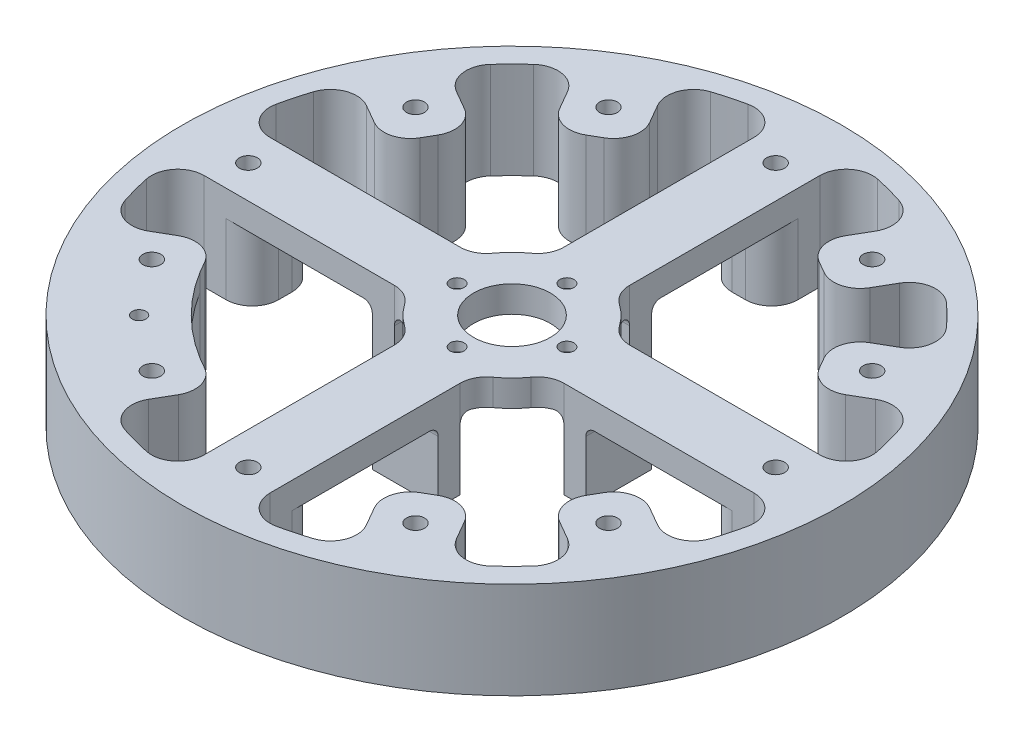
SolidWorks part; units mm, degrees
ref_plane "Front Plane" through (0, 0, 0) normal (0, 0, 1) x (1, 0, 0)
ref_plane "Top Plane" through (0, 0, 0) normal (0, 1, 0) x (1, 0, 0)
ref_plane "Right Plane" through (0, 0, 0) normal (1, 0, 0) x (0, 0, -1)
sketch "Sketch4" plane through (0, 0, 0) normal (0, 1, 0) x (1, 0, 0)
  circle A0 centre (0, 0) radius 75
  circle A1 centre (0, 0) radius 70
  dimension "D1" = 150
  dimension "D2" = 5
extrude "Boss-Extrude2" add sketch "Sketch4" along normal blind 22
sketch "Sketch5" plane through (0, 22, 0) normal (0, 1, 0) x (1, 0, 0)
  line L2 (-7.5, 69.5971) -> (-7.5, 51.5971)
  line L3 (-7.5, 51.5971) -> (7.5, 51.5971)
  line L4 (7.5, 69.5971) -> (7.5, 51.5971)
  circle A0 centre (0, 0) radius 70 construction
  arc A1 (-7.5, 69.5971) -> (7.5, 69.5971) centre (0, 0) cw
  circle A2 centre (0, 60) radius 2.05
  point P6 (0, 51.5971)
  dimension "D3" = 4.1
  dimension "D1" = 15
  dimension "D2" = 18
  dimension "D4" = 60
extrude "Boss-Extrude3" add sketch "Sketch5" against normal up to surface (22 mm away) up to face at (0, 0, 75)
fillet "Fillet1" radius 6 4 edges at (7.5, 11, -69.5971) (-7.5, 11, -69.5971) (7.5, 11, -51.5971) (-7.5, 11, -51.5971)
pattern_circular "CirPattern3" count 12 over 360 about axis through (0, 22, 0) along (0, 1, 0) of "Fillet1", "Boss-Extrude3"
sketch "Sketch1" plane through (0, 0, 0) normal (0, 1, 0) x (1, 0, 0)
  circle A0 centre (0, 0) radius 55
  circle A1 centre (0, 0) radius 75
  dimension "D1" = 150
  dimension "D2" = 110
extrude "Boss-Extrude1" [suppressed] add sketch "Sketch1" along normal blind 21.08
sketch "Sketch2" [suppressed] plane through (0, 21.08, 0) normal (0, 1, 0) x (1, 0, 0)
  circle A0 centre (0, 60) radius 2.05
  circle A1 centre (30, 51.9615) radius 2.05
  circle A2 centre (51.9615, 30) radius 2.05
  circle A3 centre (60, 0) radius 2.05
  circle A4 centre (51.9615, -30) radius 2.05
  circle A5 centre (30, -51.9615) radius 2.05
  circle A6 centre (0, -60) radius 2.05
  circle A7 centre (-30, -51.9615) radius 2.05
  circle A8 centre (-51.9615, -30) radius 2.05
  circle A9 centre (-60, 0) radius 2.05
  circle A10 centre (-51.9615, 30) radius 2.05
  circle A11 centre (-30, 51.9615) radius 2.05
  point P27 (0, 0)
  dimension "D1" = 4.1
  dimension "D2" = 60
  dimension "D3" = 12
extrude "Cut-Extrude1" [suppressed] cut sketch "Sketch2" against normal through all
sketch "Sketch3" [suppressed] plane through (0, 21.08, 0) normal (0, 1, 0) x (1, 0, 0)
  line L0 (0, 0) -> (0, 60) construction
  line L1 (0, 0) -> (30, 51.9615) construction
  line L2 (0, 0) -> (16.8232, 62.7852) construction
  circle A0 centre (16.8232, 62.7852) radius 7.5
  circle A1 centre (0, 0) radius 65 construction
  circle A2 centre (45.9619, 45.9619) radius 7.5
  circle A3 centre (62.7852, 16.8232) radius 7.5
  circle A4 centre (62.7852, -16.8232) radius 7.5
  circle A5 centre (45.9619, -45.9619) radius 7.5
  circle A6 centre (16.8232, -62.7852) radius 7.5
  circle A7 centre (-16.8232, -62.7852) radius 7.5
  circle A8 centre (-45.9619, -45.9619) radius 7.5
  circle A9 centre (-62.7852, -16.8232) radius 7.5
  circle A10 centre (-62.7852, 16.8232) radius 7.5
  circle A11 centre (-45.9619, 45.9619) radius 7.5
  circle A12 centre (-16.8232, 62.7852) radius 7.5
  point P30 (0, 0)
  dimension "D1" = 15
  dimension "D2" = 130
  dimension "D4" = 15
  dimension "D3" = 12
extrude "Cut-Extrude2" [suppressed] cut sketch "Sketch3" against normal through all
sketch "Sketch6" plane through (0, 22, 0) normal (0, 1, 0) x (1, 0, 0)
  line L0 (-7.5, 57.5971) -> (-7.5, 15.8667)
  line L1 (7.5, 57.5971) -> (7.5, 15.8667)
  line L2 (57.5971, 7.5) -> (15.8667, 7.5)
  line L3 (-57.5971, -7.5) -> (-15.8667, -7.5)
  line L5 (7.5, -15.8667) -> (7.5, -57.5971)
  line L6 (-7.5, -15.8667) -> (-7.5, -57.5971)
  line L7 (-15.8667, 7.5) -> (-57.5971, 7.5)
  line L8 (15.8667, -7.5) -> (57.5971, -7.5)
  line L9 (-57.5971, 7.5) -> (-57.5971, -7.5)
  line L10 (-7.5, -57.5971) -> (7.5, -57.5971)
  line L11 (57.5971, 7.5) -> (57.5971, -7.5)
  line L12 (-7.5, 57.5971) -> (7.5, 57.5971)
  arc A0 (-51.5971, 1.5) -> (-57.5971, 7.5) centre (-57.5971, 1.5) ccw construction
  arc A1 (7.5, -15.8667) -> (15.8667, -7.5) centre (0, 0) ccw
  arc A2 (15.8667, 7.5) -> (7.5, 15.8667) centre (0, 0) ccw
  arc A3 (-7.5, 15.8667) -> (-15.8667, 7.5) centre (0, 0) ccw
  arc A4 (-15.8667, -7.5) -> (-7.5, -15.8667) centre (0, 0) ccw
  circle A5 centre (-12.5, 0) radius 1.6
  circle A6 centre (0, 12.5) radius 1.6
  circle A7 centre (12.5, 0) radius 1.6
  circle A8 centre (0, -12.5) radius 1.6
  circle A9 centre (0, 0) radius 8.75
  point P40 (0, 0)
  dimension "D1" = 35.1
  dimension "D2" = 3.2
  dimension "D5" = 17.5
  dimension "D3" = 12.5
  dimension "D4" = 4
extrude "Boss-Extrude4" add sketch "Sketch6" against normal blind 6
sketch "Sketch7" plane through (0, 16, 0) normal (0, -1, 0) x (1, 0, 0)
  circle A0 centre (0, 12.5) radius 3.5
  circle A1 centre (12.5, 0) radius 3.5
  circle A2 centre (0, -12.5) radius 3.5
  circle A3 centre (-12.5, 0) radius 3.5
  point P12 (0, 0)
  dimension "D1" = 7
  dimension "D2" = 4
extrude "Cut-Extrude3" cut sketch "Sketch7" against normal blind 3.9
chamfer "Chamfer1" distance 1.9 angle 45 4 edges at (-12.5, 19.9, -3.5) (0, 19.9, -16) (12.5, 19.9, -3.5) (0, 19.9, 9)
fillet "Fillet2" radius 6 8 edges at (-7.5, 19, 15.8667) (-15.8667, 19, 7.5) (-15.8667, 19, -7.5) (-7.5, 19, -15.8667) (7.5, 19, -15.8667) (15.8667, 19, -7.5) (15.8667, 19, 7.5) (7.5, 19, 15.8667)
sketch "Sketch8" plane through (0, 16, 0) normal (0, -1, 0) x (1, 0, 0)
  line L0 (-19.2964, -7.5) -> (-57.5971, -7.5) construction
  line L1 (-19.2964, 7.5) -> (-24.2964, 7.5)
  line L2 (-19.2964, 7.5) -> (-19.2964, -7.5)
  line L3 (-19.2964, -7.5) -> (-24.2964, -7.5)
  line L4 (-24.2964, 7.5) -> (-24.2964, -7.5)
  line L5 (7.5, 57.5971) -> (7.5, 19.2964) construction
  line L6 (-7.5, 19.2964) -> (7.5, 19.2964)
  line L7 (-7.5, 19.2964) -> (-7.5, 24.2964)
  line L8 (-7.5, 24.2964) -> (7.5, 24.2964)
  line L9 (7.5, 19.2964) -> (7.5, 24.2964)
  line L10 (57.5971, -7.5) -> (19.2964, -7.5) construction
  line L11 (19.2964, 7.5) -> (24.2964, 7.5)
  line L12 (19.2964, 7.5) -> (19.2964, -7.5)
  line L13 (19.2964, -7.5) -> (24.2964, -7.5)
  line L14 (24.2964, 7.5) -> (24.2964, -7.5)
  line L15 (-7.5, -57.5971) -> (-7.5, -19.2964) construction
  line L16 (7.5, -19.2964) -> (-7.5, -19.2964)
  line L17 (7.5, -19.2964) -> (7.5, -24.2964)
  line L18 (7.5, -24.2964) -> (-7.5, -24.2964)
  line L19 (-7.5, -19.2964) -> (-7.5, -24.2964)
  dimension "D1" = 5
  dimension "D2" = 5
  dimension "D3" = 5
  dimension "D4" = 5
extrude "Boss-Extrude5" add sketch "Sketch8" along normal up to surface (16 mm away) up to face at (0, 0, 75)
fillet "Fillet4" radius 2 8 edges at (0, 16, -19.2964) (19.2964, 16, 0) (-19.2964, 16, 0) (0, 16, 19.2964) (0, 16, 24.2964) (24.2964, 16, 0) (0, 16, -24.2964) (-24.2964, 16, 0)
sketch "Sketch9" plane through (0, 22, 0) normal (0, 1, 0) x (1, 0, 0)
  line L4 (-50.4285, -37.7752) -> (-46.1305, -35.2937) construction
  line L5 (-35.2937, -46.1305) -> (-37.7752, -50.4285) construction
  line L6 (-50.4285, -37.7752) -> (-46.1305, -35.2937)
  line L7 (-35.2937, -46.1305) -> (-37.7752, -50.4285)
  line L8 (-42.4264, -42.4264) -> (0, 0) construction
  line L9 (0, 0) -> (-30, -51.9615) construction
  arc A1 (-43.9344, -27.0976) -> (-27.0976, -43.9344) centre (0, 0) ccw
  arc A2 (-27.0976, -43.9344) -> (-35.2937, -46.1305) centre (-30.0976, -49.1305) ccw construction
  arc A3 (-46.1305, -35.2937) -> (-43.9344, -27.0976) centre (-49.1305, -30.0976) ccw construction
  arc A4 (-46.1305, -35.2937) -> (-43.9344, -27.0976) centre (-49.1305, -30.0976) ccw
  arc A5 (-27.0976, -43.9344) -> (-35.2937, -46.1305) centre (-30.0976, -49.1305) ccw
  circle A6 centre (-42.4264, -42.4264) radius 1.55
  arc A8 (-51.8749, -46.9999) -> (-46.9999, -51.8749) centre (0, 0) ccw construction
  arc A9 (-50.4285, -37.7752) -> (-51.8749, -46.9999) centre (-47.4285, -42.9713) ccw construction
  arc A10 (-46.9999, -51.8749) -> (-37.7752, -50.4285) centre (-42.9713, -47.4285) ccw construction
  arc A11 (-50.4285, -37.7752) -> (-51.8749, -46.9999) centre (-47.4285, -42.9713) ccw
  arc A12 (-51.8749, -46.9999) -> (-46.9999, -51.8749) centre (0, 0) ccw
  arc A13 (-46.9999, -51.8749) -> (-37.7752, -50.4285) centre (-42.9713, -47.4285) ccw
  dimension "D1" = 3.1
  dimension "D2" = 60
  dimension "D3" = 15
extrude "Boss-Extrude6" add sketch "Sketch9" against normal blind 4
